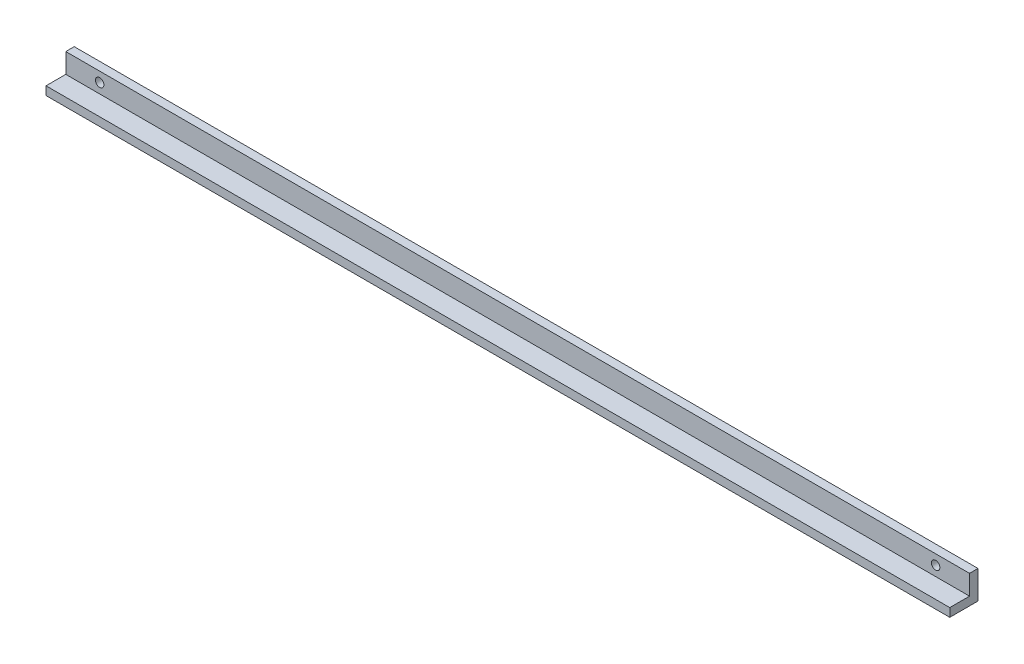
SolidWorks part; units mm, degrees
ref_plane "Спереди" through (0, 0, 0) normal (0, 0, 1) x (1, 0, 0)
ref_plane "Сверху" through (0, 0, 0) normal (0, 1, 0) x (1, 0, 0)
ref_plane "Справа" through (0, 0, 0) normal (1, 0, 0) x (0, 0, -1)
sketch "Эскиз1" plane through (0, 0, 0) normal (1, 0, 0) x (0, 0, -1)
  line L0 (0, 0) -> (-10, 0)
  line L1 (-10, 0) -> (-10, 3)
  line L2 (-10, 3) -> (-3, 3)
  line L3 (-3, 10) -> (-3, 3)
  line L6 (-3, 10) -> (0, 10)
  line L7 (0, 10) -> (0, 0)
  dimension "D1" = 3
  dimension "D2" = 10
extrude "Бобышка-Вытянуть1" add sketch "Эскиз1" along normal blind 320
sketch "Эскиз2" plane through (0, 0, 3) normal (0, 0, 1) x (1, 0, 0)
  line L0 (160, 10) -> (160, 3) construction
  line L1 (320, 10) -> (0, 10) construction
  line L2 (320, 3) -> (0, 3) construction
  line L3 (0, 10) -> (0, 3) construction
  circle A0 centre (12, 6.5) radius 1.5
  circle A1 centre (308, 6.5) radius 1.5
  dimension "D1" = 3
  dimension "D2" = 12
extrude "Вырез-Вытянуть1" cut sketch "Эскиз2" against normal through all
